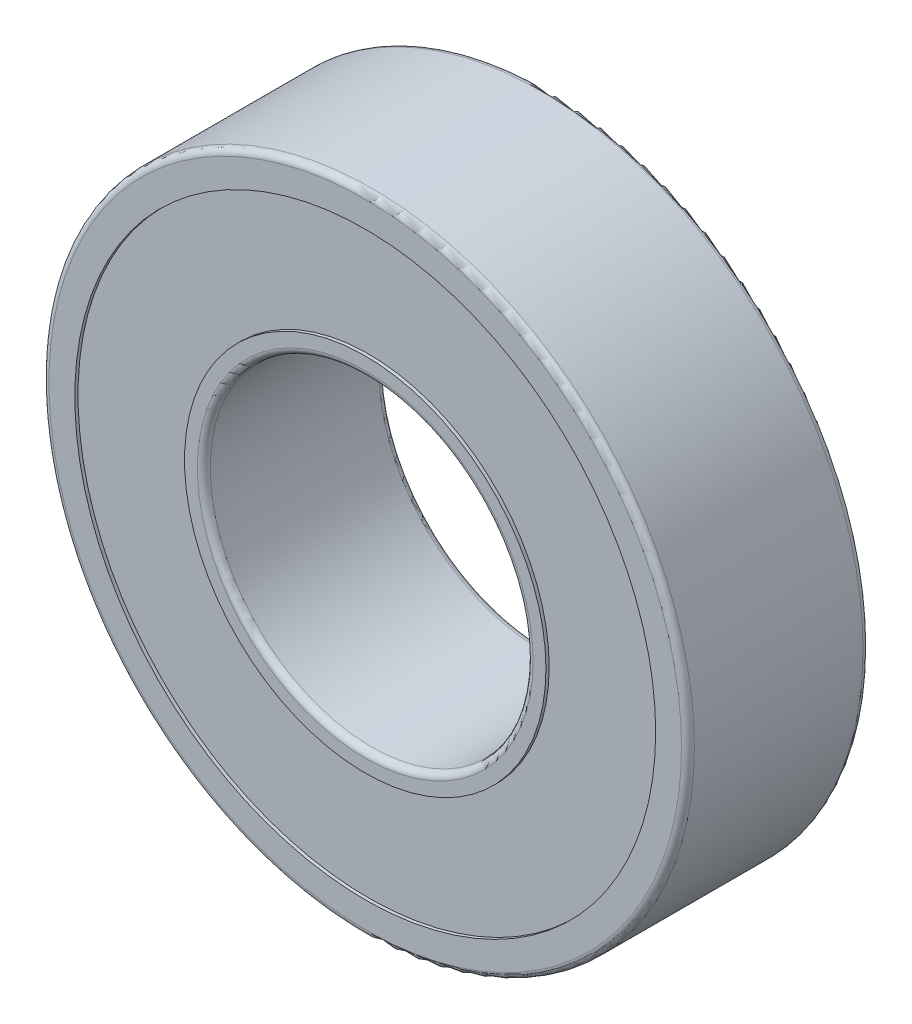
SolidWorks part; units mm, degrees
ref_plane "Front Plane" through (0, 0, 0) normal (0, 0, 1) x (1, 0, 0)
ref_plane "Top Plane" through (0, 0, 0) normal (0, 1, 0) x (1, 0, 0)
ref_plane "Right Plane" through (0, 0, 0) normal (1, 0, 0) x (0, 0, -1)
sketch "Sketch3" plane through (0, 0, 0) normal (0, 0, 1) x (1, 0, 0)
  circle A0 centre (147.7336, -1.253) radius 12.7
  circle A1 centre (147.7336, -1.253) radius 14.224
  circle A2 centre (147.7336, -1.253) radius 22.86
  circle A3 centre (147.7336, -1.253) radius 25.4
  dimension "D1" = 25.4
  dimension "D2" = 50.8
  dimension "D3" = 45.72
  dimension "D4" = 28.448
extrude "Boss-Extrude1" add sketch "Sketch3" along normal blind 14.2875 contours A3 A2 | A1 A0 region at (133.9119, -1.253, 0) region at (123.052, -1.253, 0)
extrude "Boss-Extrude2" add sketch "Sketch3<3>" along normal blind 13.7795 from offset 0.254 separate body contours A2 A1 region at (125.5202, -1.253, 0)
sketch "Sketch3<3>" plane through (0, 0, 0) normal (0, 0, 1) x (1, 0, 0) same geometry as "Sketch3"
fillet "Fillet1" radius 0.508 2 edges at (160.4336, -1.253, 14.2875) (160.4336, -1.253, 0)
fillet "Fillet2" radius 0.508 2 edges at (173.1336, -1.253, 14.2875) (173.1336, -1.253, 0)
